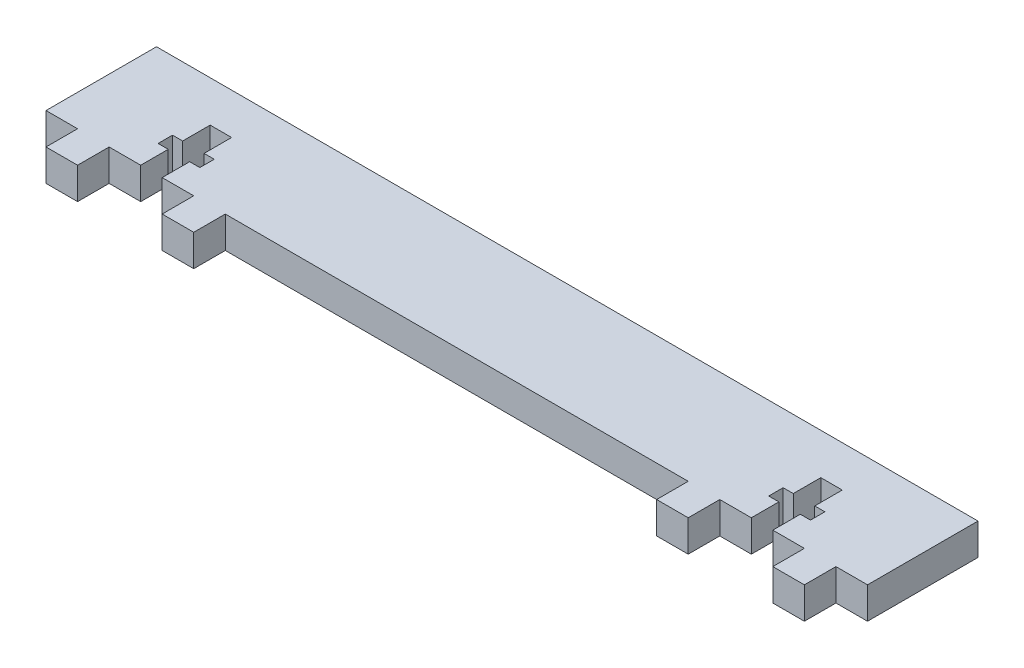
SolidWorks part; units mm, degrees
ref_plane "Front Plane" through (0, 0, 0) normal (0, 0, 1) x (1, 0, 0)
ref_plane "Top Plane" through (0, 0, 0) normal (0, 1, 0) x (1, 0, 0)
ref_plane "Right Plane" through (0, 0, 0) normal (1, 0, 0) x (0, 0, -1)
sketch "Sketch1" plane through (0, 0, 0) normal (0, 1, 0) x (1, 0, 0)
  line L0 (0, 11.1125) -> (0, -11.1125) construction
  line L1 (-82.6262, -11.1125) -> (-76.2762, -11.1125)
  line L2 (-82.6262, -11.1125) -> (-82.6262, 11.1125)
  line L3 (-82.6262, 11.1125) -> (82.6262, 11.1125)
  line L4 (82.6262, -11.1125) -> (82.6262, 11.1125)
  line L5 (-82.6262, -11.1125) -> (82.6262, 11.1125) construction
  line L6 (-82.6262, 11.1125) -> (82.6262, -11.1125) construction
  line L7 (-46.5582, -11.1125) -> (46.5582, -11.1125)
  line L8 (82.6262, -11.1125) -> (76.2762, -11.1125)
  point P0 (0, 0)
  line B0 (-69.9262, -11.1125) -> (-69.9262, -17.4625)
  line B1 (-69.9262, -17.4625) -> (-76.2762, -17.4625)
  line B2 (-76.2762, -17.4625) -> (-76.2762, -11.1125)
  line B3 (-63.5762, -11.1125) -> (-63.5762, -5.5775)
  line B4 (-63.5762, -5.5775) -> (-65.6172, -5.5775)
  line B5 (-65.6172, -5.5775) -> (-65.6172, -2.6775)
  line B6 (-65.6172, -2.6775) -> (-63.5762, -2.6775)
  line B7 (-63.5762, -2.6775) -> (-63.5762, 2.8575)
  line B8 (-63.5762, 2.8575) -> (-59.2582, 2.8575)
  line B9 (-59.2582, 2.8575) -> (-59.2582, -2.6775)
  line B10 (-59.2582, -2.6775) -> (-57.2172, -2.6775)
  line B11 (-57.2172, -2.6775) -> (-57.2172, -5.5775)
  line B12 (-57.2172, -5.5775) -> (-59.2582, -5.5775)
  line B13 (-59.2582, -5.5775) -> (-59.2582, -11.1125)
  line B14 (-61.4172, 2.8575) -> (-61.4172, -11.1125) construction
  line B15 (-52.9082, -11.1125) -> (-59.2582, -11.1125)
  line B16 (-46.5582, -17.4625) -> (-46.5582, -11.1125)
  line B17 (-69.9262, -11.1125) -> (-63.5762, -11.1125)
  line B18 (-52.9082, -17.4625) -> (-46.5582, -17.4625)
  line B19 (-52.9082, -11.1125) -> (-52.9082, -17.4625)
  line B20 (69.9262, -11.1125) -> (69.9262, -17.4625)
  line B21 (69.9262, -17.4625) -> (76.2762, -17.4625)
  line B22 (76.2762, -17.4625) -> (76.2762, -11.1125)
  line B23 (63.5762, -11.1125) -> (63.5762, -5.5775)
  line B24 (63.5762, -5.5775) -> (65.6172, -5.5775)
  line B25 (65.6172, -5.5775) -> (65.6172, -2.6775)
  line B26 (65.6172, -2.6775) -> (63.5762, -2.6775)
  line B27 (63.5762, -2.6775) -> (63.5762, 2.8575)
  line B28 (63.5762, 2.8575) -> (59.2582, 2.8575)
  line B29 (59.2582, 2.8575) -> (59.2582, -2.6775)
  line B30 (59.2582, -2.6775) -> (57.2172, -2.6775)
  line B31 (57.2172, -2.6775) -> (57.2172, -5.5775)
  line B32 (57.2172, -5.5775) -> (59.2582, -5.5775)
  line B33 (59.2582, -5.5775) -> (59.2582, -11.1125)
  line B34 (61.4172, 2.8575) -> (61.4172, -11.1125) construction
  line B35 (52.9082, -11.1125) -> (59.2582, -11.1125)
  line B36 (46.5582, -17.4625) -> (46.5582, -11.1125)
  line B37 (69.9262, -11.1125) -> (63.5762, -11.1125)
  line B38 (52.9082, -17.4625) -> (46.5582, -17.4625)
  line B39 (52.9082, -11.1125) -> (52.9082, -17.4625)
  dimension "D1" = 22.225
  dimension "D2" = 93.1164
  dimension "D3" = 6.35
sketch_block_instance "Male T-slot assembly-1"
sketch_block "Male T-slot assembly" parameters "D1"=6.35, "D2"=6.35, "D3"=4.318, "D4"=2.9, "D5"=8.4, "D6"=13.97, "D7"=6.35
sketch_block_instance "Male T-slot assembly-3"
extrude "Boss-Extrude1" add sketch "Sketch1" along normal blind 6.35 contours B39 B35 B33 B32 B31 B30 B29 B28 B27 B26 B25 B24 B23 B37 B20 B21 B22 L8 L4 L3 L2 L1 B2 B1 B0 B17 B3 B4 B5 B6 B7 B8 B9 B10 B11 B12 B13 B15 B19 B18 B16 L7 B36 B38 region at (0, 0, 0.4631)
equation "\"Ball Diameter\"= 1.75in"
equation "\"Ball Radius\" = \"Ball Diameter\"/2"
equation "\"Sheet Thickness\"= 0.25in"
equation "\"Screw Diameter\"= .17in"
equation "\"Robot Diameter\"= 14in"
equation "\"Castor Screw Diameter\"= 0.22in"
equation "\"Wheel Diameter\" = 4in"
equation "\"Nut Diameter\" = 8.4mm"
equation "\"Nut Height\" = 2.9mm"
equation "\"Screw Height\" = 0.55in"
equation "\"Pulley Diameter\" = 1in"
equation "\"Reactor Height\" = 14in"
equation "\"Elevator Height\" = 11.5in"
equation "\"Elevator Width\" = \"Ball Diameter\" + 0.25in"
equation "\"Elevator Bearing Diameter\" = sqr(2*(\"Sheet Thickness\"^2)) + 0.2in"
equation "\"Elevator Axle Endcap Diameter\" = \"Pulley Diameter\" + 0.25in"
equation "\"Elevator Axle Length\" = \"Elevator Width\" + 8*\"Sheet Thickness\""
equation "\"Elevator Clearance from Axis\" = 3.5in"
equation "\"Elevator Horizontal Clearance\" = \"Elevator Width\" + 0.5in"
equation "\"Claw Horizontal Seperation\" = (\"Elevator Width\"/2) - (1.5 * \"Sheet Thickness\") - 0.15in"
equation "\"Claw Radius\" = \"Ball Radius\" + 0.1in"
equation "\"Castor Wheel Height\" = 1.25in"
equation "\"Length of Chute\" = 8in"
equation "\"D1@Sketch1\"=\"Ball Radius\""
